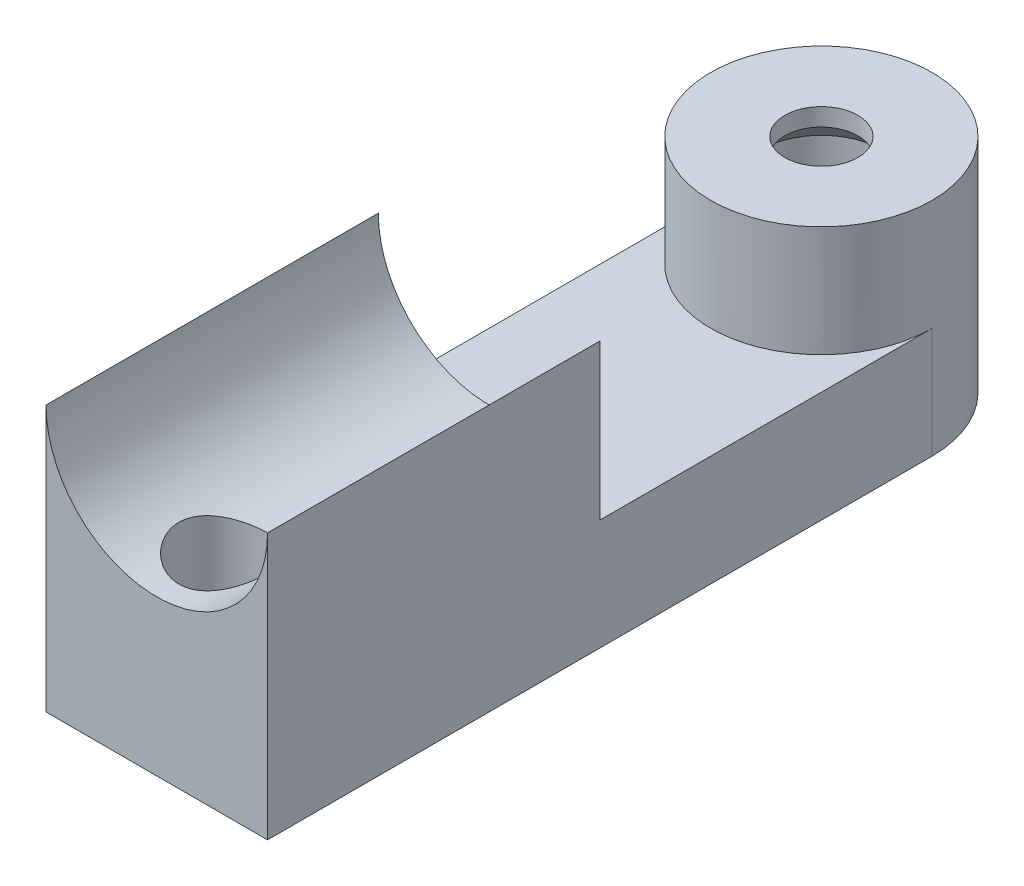
SolidWorks part; units mm, degrees
ref_plane "Front Plane" through (0, 0, 0) normal (0, 0, 1) x (1, 0, 0)
ref_plane "Top Plane" through (0, 0, 0) normal (0, 1, 0) x (1, 0, 0)
ref_plane "Right Plane" through (0, 0, 0) normal (1, 0, 0) x (0, 0, -1)
sketch "Sketch1" plane through (0, 0, 0) normal (0, 1, 0) x (1, 0, 0)
  circle A0 centre (0, 0) radius 5
  circle A1 centre (0, 0) radius 1.65
  dimension "D1" = 3.3
  dimension "D2" = 10
extrude "Boss-Extrude1" add sketch "Sketch1" along normal blind 5
sketch "Sketch2" plane through (0, 0, 0) normal (0, -1, 0) x (1, 0, 0)
  line L0 (-5, 0) -> (-5, 30)
  line L1 (-5, 30) -> (5, 30)
  line L2 (5, 30) -> (5, 0)
  circle A1 centre (0, 0) radius 5
  arc A2 (-5, 0) -> (5, 0) centre (0, 0) ccw
  dimension "D2" = 30
  dimension "D1" = 0
extrude "Boss-Extrude2" add sketch "Sketch2" along normal blind 5
sketch "Sketch3" plane through (0, 0, 30) normal (0, 0, 1) x (1, 0, 0)
  line L0 (-5, 0) -> (-5, 7)
  line L1 (5, 0) -> (5, 7)
  line L4 (5, 0) -> (-5, 0)
  line L5 (-5, 0) -> (-5, -5)
  line L6 (-5, -5) -> (5, -5)
  line L7 (5, -5) -> (5, 0)
  line L9 (-5, 0) -> (-5, -5)
  line L10 (-5, -5) -> (5, -5)
  line L11 (5, -5) -> (5, 0)
  arc A2 (-5, 7) -> (5, 7) centre (0, 7) ccw
  point P2 (0, 7)
  dimension "D1" = 0
extrude "Boss-Extrude3" add sketch "Sketch3" against normal blind 15
sketch "Sketch4" plane through (0, -5, 0) normal (0, -1, 0) x (1, 0, 0)
  line L0 (5, 30) -> (-5, 30) construction
  circle A0 centre (0, 27) radius 2
  dimension "D1" = 4
  dimension "D2" = 3
extrude "Cut-Extrude1" cut sketch "Sketch4" against normal through all from offset 1.9 offset against normal yes
sketch "Sketch6" plane through (0, -5, 0) normal (0, -1, 0) x (1, 0, 0)
  circle A0 centre (0, 0) radius 2.75
  dimension "D1" = 5.5
extrude "Cut-Extrude2" cut sketch "Sketch6" against normal blind 8
chamfer "Chamfer1" distance 1.2 angle 45 1 edges at (0, 3, -1.65)
